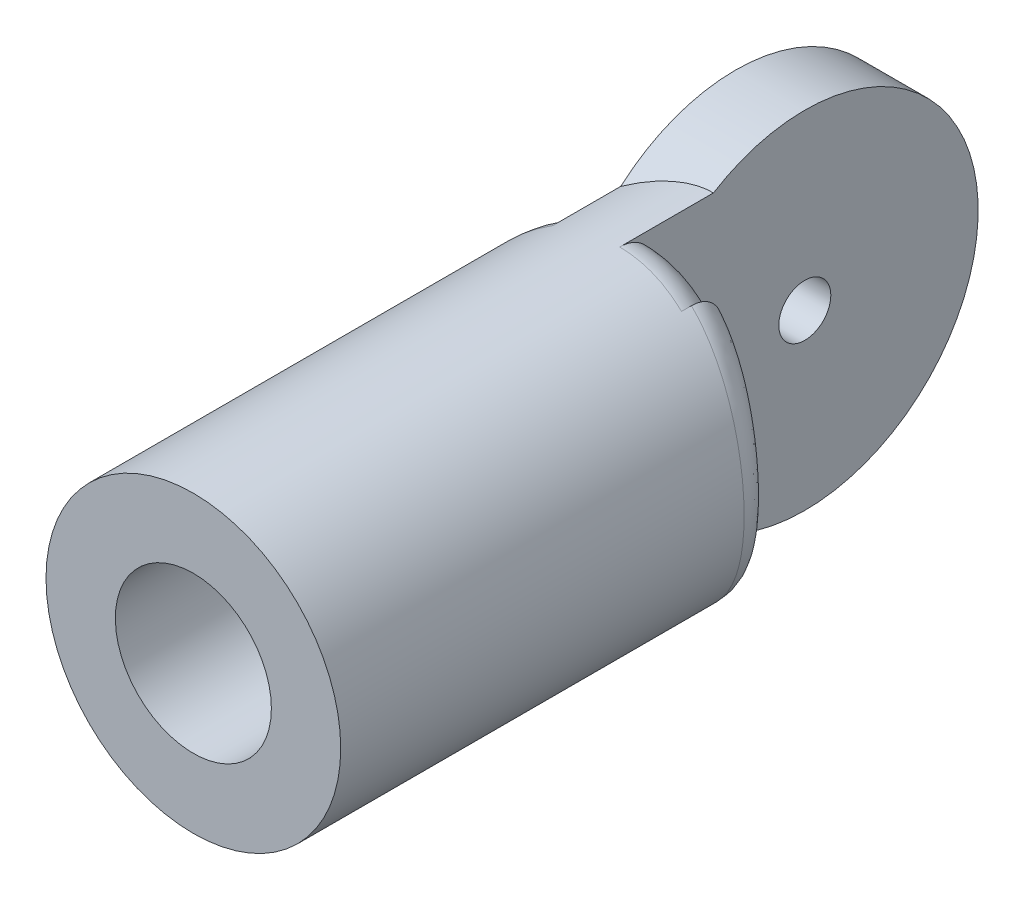
SolidWorks part; units mm, degrees
ref_plane "Спереди" through (0, 0, 0) normal (0, 0, 1) x (1, 0, 0)
ref_plane "Сверху" through (0, 0, 0) normal (0, 1, 0) x (1, 0, 0)
ref_plane "Справа" through (0, 0, 0) normal (1, 0, 0) x (0, 0, -1)
sketch "Sketch1" plane through (0, 0, 0) normal (0, 0, 1) x (1, 0, 0)
  circle A0 centre (0, 0) radius 4.5
  circle A1 centre (0, 0) radius 8.5
  dimension "D1" = 9
  dimension "D2" = 4
extrude "Boss-Extrude1" add sketch "Sketch1" along normal blind 30
sketch "Sketch2" plane through (0, 0, 0) normal (1, 0, 0) x (0, 0, -1)
  circle A0 centre (5.2678, 0) radius 10
  dimension "D1" = 20
extrude "Boss-Extrude2" add sketch "Sketch2" along normal mid plane 8
sketch "Sketch4" plane through (-4, 0, 0) normal (-1, 0, 0) x (0, 0, 1)
  circle A0 centre (-5.2678, 0) radius 1.5
  dimension "D1" = 3
extrude "Cut-Extrude1" cut sketch "Sketch4" against normal mid plane 34
sketch "Sketch5" plane through (4, 0, 0) normal (1, 0, 0) x (0, 0, -1)
  circle A0 centre (5.2678, 0) radius 10
extrude "Cut-Extrude2" cut sketch "Sketch5" along normal blind 31
sketch "Sketch6" plane through (-4, 0, 0) normal (-1, 0, 0) x (0, 0, 1)
  circle A0 centre (-5.2678, 0) radius 10
extrude "Cut-Extrude3" cut sketch "Sketch6" along normal blind 25
fillet "Fillet3" radius 2 2 edges at (8.4076, -1.2498, 4.6538) (-8.4076, 1.2498, 4.6538)
sketch "Sketch8" plane through (4, 0, 0) normal (1, 0, 0) x (0, 0, -1)
  circle A0 centre (5.2678, 0) radius 10.5
  dimension "D1" = 21
extrude "Cut-Extrude4" cut sketch "Sketch8" against normal blind 4
fillet "Fillet4" radius 2 2 edges at (1.84, -8.2985, 1.1653) (2.0451, 8.2503, 1.227)
